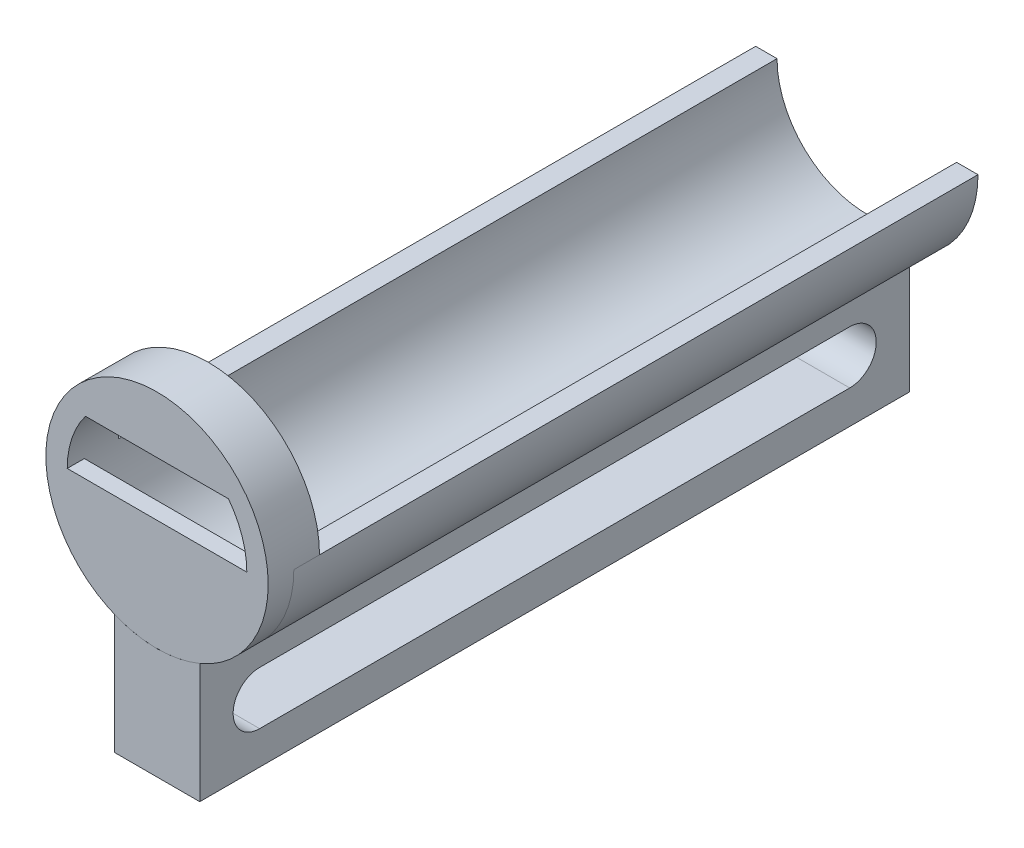
SolidWorks part; units mm, degrees
ref_plane "前视基准面" through (0, 0, 0) normal (0, 0, 1) x (1, 0, 0)
ref_plane "上视基准面" through (0, 0, 0) normal (0, 1, 0) x (1, 0, 0)
ref_plane "右视基准面" through (0, 0, 0) normal (1, 0, 0) x (0, 0, -1)
other "Configuration Table"
sketch "草图2" plane through (0, 0, 0) normal (0, 0, 1) x (1, 0, 0)
  circle A0 centre (8236.9694, 2993.6134) radius 10.5
  circle A4 centre (8236.9694, 2993.6134) radius 13
extrude "凸台-拉伸1" add sketch "草图2" along normal blind 3
sketch "草图3" plane through (0, 0, 3) normal (0, 0, 1) x (1, 0, 0)
  line L0 (8247.4694, 2993.6134) -> (8226.4694, 2993.6134)
  line L1 (8228.6079, 2999.9643) -> (8245.331, 2999.9643)
  arc A0 (8226.4694, 2993.6134) -> (8247.4694, 2993.6134) centre (8236.9694, 2993.6134) ccw
  arc A1 (8245.331, 2999.9643) -> (8228.6079, 2999.9643) centre (8236.9694, 2993.6134) ccw
extrude "凸台-拉伸3" add sketch "草图3" against normal blind 2
sketch "草图5" plane through (0, 0, 0) normal (0, 0, -1) x (-1, 0, 0)
  line L0 (-8247.4694, 2993.6134) -> (-8226.4694, 2993.6134) construction
  line L1 (-8247.4694, 2993.6134) -> (-8249.9689, 2993.6134)
  line L2 (-8226.4694, 2993.6134) -> (-8223.97, 2993.6134)
  arc A0 (-8247.4694, 2993.6134) -> (-8226.4694, 2993.6134) centre (-8236.9694, 2993.6134) ccw
  arc A1 (-8249.9689, 2993.6134) -> (-8223.97, 2993.6134) centre (-8236.9694, 2993.6134) ccw
extrude "凸台-拉伸5" add sketch "草图5" along normal blind 80
sketch "草图6" plane through (0, 0, 0) normal (0, 0, -1) x (-1, 0, 0)
  line L0 (-8247.4694, 2993.6134) -> (-8226.4694, 2993.6134) construction
  line L1 (-8249.9694, 2993.6134) -> (-8247.4694, 2993.6134)
  line L2 (-8226.4694, 2993.6134) -> (-8223.9694, 2993.6134)
  arc A0 (-8223.9694, 2993.6134) -> (-8249.9694, 2993.6134) centre (-8236.9694, 2993.6134) ccw
  arc A1 (-8226.4694, 2993.6134) -> (-8247.4694, 2993.6134) centre (-8236.9694, 2993.6134) ccw
extrude "凸台-拉伸6" add sketch "草图6" along normal blind 3
sketch "草图7" plane through (0, 2993.6134, 0) normal (0, 1, 0) x (1, 0, 0)
  line L0 (8223.9694, -3) -> (8249.9694, -3) construction
  line L1 (8231.9694, -3) -> (8241.9694, -3)
  line L2 (8231.9694, -3) -> (8231.9694, 80)
  line L3 (8231.9694, 80) -> (8241.9694, 80)
  line L4 (8241.9694, -3) -> (8241.9694, 80)
  line L5 (8247.4694, 80) -> (8226.4694, 80) construction
  line L6 (8226.4694, 80) -> (8226.4694, 3) construction
  dimension "D1" = 10
  dimension "D2" = 5.5
extrude "凸台-拉伸8" add sketch "草图7" against normal blind 26 separate body
sketch "草图8" plane through (8231.9694, 0, 0) normal (-1, 0, 0) x (0, 0, 1)
  line L0 (-80, 2967.6134) -> (-80, 2993.6134) construction
  line L1 (3, 2967.6134) -> (3, 2993.6134) construction
  line L2 (-80, 2967.6134) -> (3, 2967.6134) construction
  line L3 (-73, 2977.7134) -> (-4, 2977.7134)
  line L4 (-73, 2971.5134) -> (-4, 2971.5134)
  arc A0 (-73, 2977.7134) -> (-73, 2971.5134) centre (-73, 2974.6134) ccw
  arc A1 (-4, 2971.5134) -> (-4, 2977.7134) centre (-4, 2974.6134) ccw
  dimension "D1" = 7
  dimension "D4" = 6.2
  dimension "D5" = 6.2
  dimension "D2" = 7
  dimension "D3" = 7
extrude "凸台-拉伸9" add sketch "草图8" against normal blind 18 separate body
combine bodies "组合1" operation type subtract main body 123 bodies to subtract 124
sketch "草图9" plane through (0, 0, -3) normal (0, 0, -1) x (-1, 0, 0)
  line L0 (-8241.9694, 2993.6134) -> (-8231.9694, 2993.6134) construction
  circle A0 centre (-8236.9694, 2993.6134) radius 13
extrude "凸台-拉伸10" add sketch "草图9" along normal mid plane 188 separate body
combine bodies "组合2" operation type subtract main body 125 bodies to subtract 126
